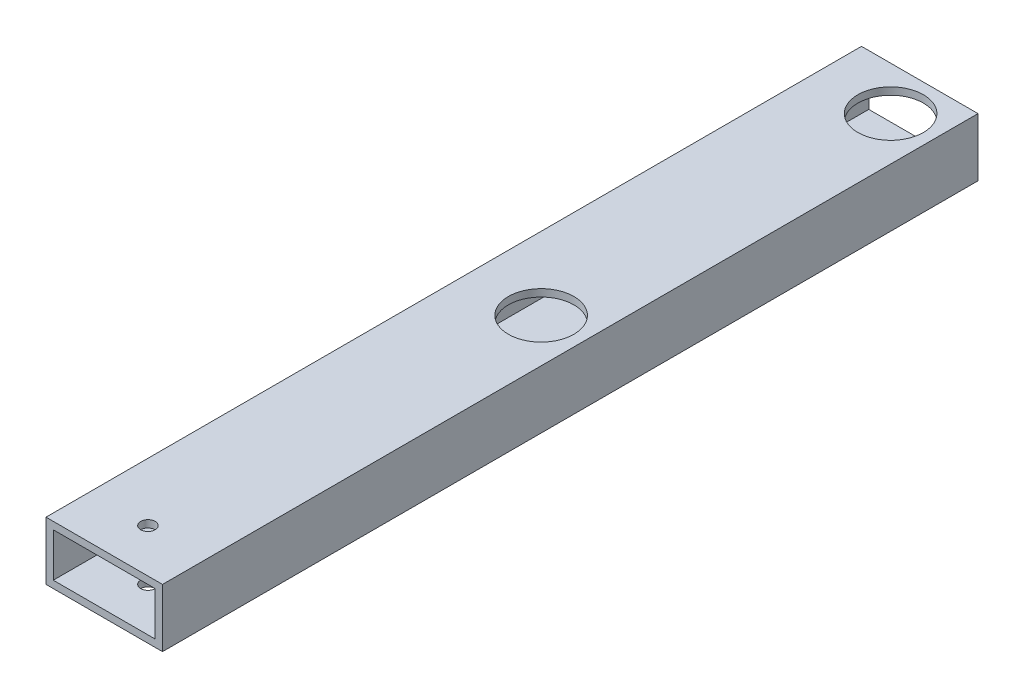
SolidWorks part; units mm, degrees
ref_plane "Front" through (0, 0, 0) normal (0, 0, 1) x (1, 0, 0)
ref_plane "Top" through (0, 0, 0) normal (0, 1, 0) x (1, 0, 0)
ref_plane "Right" through (0, 0, 0) normal (1, 0, 0) x (0, 0, -1)
sketch "Sketch1" plane through (0, 0, 0) normal (0, 0, 1) x (1, 0, 0)
  line L0 (3.175, 3.175) -> (47.625, 3.175)
  line L1 (0, 0) -> (50.8, 0)
  line L2 (0, 0) -> (0, 25.4)
  line L3 (0, 25.4) -> (50.8, 25.4)
  line L4 (50.8, 0) -> (50.8, 25.4)
  line L5 (47.625, 3.175) -> (47.625, 22.225)
  line L6 (3.175, 22.225) -> (47.625, 22.225)
  line L7 (3.175, 3.175) -> (3.175, 22.225)
  dimension "D1" = 25.4
  dimension "D2" = 50.8
  dimension "D3" = 3.175
extrude "Boss-Extrude1" add sketch "Sketch1" along normal blind 355.6
sketch "Sketch2" plane through (0, 25.4, 0) normal (0, 1, 0) x (1, 0, 0)
  line L0 (31.75, 0) -> (31.75, -19.05) construction
  line L2 (31.75, -19.05) -> (31.75, -171.45) construction
  line L4 (50.8, -355.6) -> (50.8, 0) construction
  line L5 (50.8, 0) -> (0, 0) construction
  circle A0 centre (31.75, -19.05) radius 14.2875
  circle A1 centre (31.75, -171.45) radius 14.2875
  point P4 (0, 0)
  dimension "D1" = 28.575
  dimension "D4" = 28.575
  dimension "D2" = 19.05
  dimension "D3" = 152.4
  dimension "D5" = 19.05
extrude "Cut-Extrude1" cut sketch "Sketch2" against normal through all
sketch "Sketch3" plane through (0, 25.4, 0) normal (0, 1, 0) x (1, 0, 0)
  line L0 (25.4, -336.55) -> (25.4, -355.6) construction
  line L1 (50.8, -355.6) -> (0, -355.6) construction
  circle A0 centre (25.4, -336.55) radius 3.175
  dimension "D1" = 6.35
  dimension "D2" = 19.05
extrude "Cut-Extrude2" cut sketch "Sketch3" against normal through all
